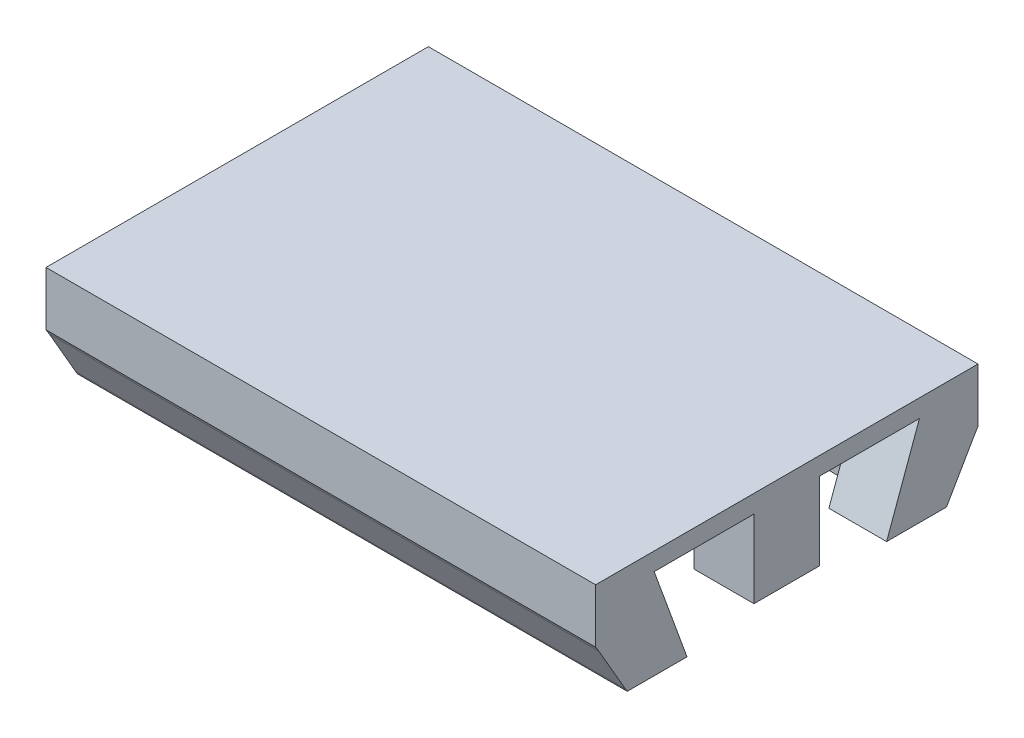
SolidWorks part; units mm, degrees
ref_plane "前视基准面" through (0, 0, 0) normal (0, 0, 1) x (1, 0, 0)
ref_plane "上视基准面" through (0, 0, 0) normal (0, 1, 0) x (1, 0, 0)
ref_plane "右视基准面" through (0, 0, 0) normal (1, 0, 0) x (0, 0, -1)
sketch "前视标记" plane through (0, 0, 0) normal (0, 0, 1) x (1, 0, 0)
  line L1 (0, 0) -> (58.42, 0)
  line L2 (0, 0) -> (0, 11.4935)
  line L3 (0, 11.4935) -> (58.42, 11.4935)
  line L4 (58.42, 0) -> (58.42, 11.4935)
sketch "上视标记" plane through (0, 0, 0) normal (0, 1, 0) x (1, 0, 0)
  line L1 (58.42, -40.64) -> (0, -40.64)
  line L3 (0, -40.64) -> (58.42, -40.64)
  line L4 (0, -40.64) -> (0, 0)
  line L5 (0, 0) -> (58.42, 0)
  line L6 (58.42, -40.64) -> (58.42, 0)
  line L7 (9.3133, -30.9271) -> (9.3133, -34.417)
  line L9 (9.3133, -6.223) -> (9.3133, -9.7129)
  line L10 (21.59, -34.417) -> (27.7283, -34.417)
  line L12 (58.42, -23.8125) -> (58.42, -16.8275)
  line L14 (58.42, -16.8275) -> (52.07, -16.8275)
  line L18 (52.07, -23.8125) -> (58.42, -23.8125)
  line L19 (52.07, -16.8275) -> (52.07, -23.8125)
  line L22 (52.2817, -30.9271) -> (52.2817, -34.417)
  line L23 (58.42, -30.9271) -> (52.2817, -30.9271)
  line L28 (46.1433, -30.9271) -> (40.005, -30.9271)
  line L30 (40.005, -30.9271) -> (40.005, -34.417)
  line L34 (46.1433, -34.417) -> (46.1433, -30.9271)
  line L35 (40.005, -34.417) -> (46.1433, -34.417)
  line L41 (33.8667, -34.417) -> (33.8667, -30.9271)
  line L42 (27.7283, -34.417) -> (33.8667, -34.417)
  line L47 (27.7283, -30.9271) -> (27.7283, -34.417)
  line L48 (33.8667, -30.9271) -> (27.7283, -30.9271)
  line L52 (21.59, -34.417) -> (21.59, -30.9271)
  line L53 (15.4517, -34.417) -> (21.59, -34.417)
  line L58 (21.59, -30.9271) -> (15.4517, -30.9271)
  line L60 (15.4517, -30.9271) -> (15.4517, -34.417)
  line L61 (3.175, -30.9271) -> (9.3133, -30.9271)
  line L63 (3.175, -9.7129) -> (3.175, -30.9271)
  line L65 (9.3133, -9.7129) -> (3.175, -9.7129)
  line L67 (9.3133, -34.417) -> (15.4517, -34.417)
  line L69 (40.005, -34.417) -> (33.8667, -34.417)
  line L71 (52.2817, -34.417) -> (46.1433, -34.417)
  line L73 (52.2817, -9.7129) -> (58.42, -9.7129)
  line L75 (52.2817, -6.223) -> (52.2817, -9.7129)
  line L77 (46.1433, -6.223) -> (52.2817, -6.223)
  line L82 (46.1433, -9.7129) -> (46.1433, -6.223)
  line L83 (40.005, -9.7129) -> (46.1433, -9.7129)
  line L88 (46.1433, -6.223) -> (40.005, -6.223)
  line L90 (40.005, -6.223) -> (40.005, -9.7129)
  line L91 (40.005, -6.223) -> (33.8667, -6.223)
  line L93 (21.59, -6.223) -> (27.7283, -6.223)
  line L98 (27.7283, -9.7129) -> (33.8667, -9.7129)
  line L100 (33.8667, -9.7129) -> (33.8667, -6.223)
  line L104 (27.7283, -6.223) -> (27.7283, -9.7129)
  line L105 (33.8667, -6.223) -> (27.7283, -6.223)
  line L107 (15.4517, -6.223) -> (9.3133, -6.223)
  line L113 (21.59, -9.7129) -> (21.59, -6.223)
  line L114 (15.4517, -9.7129) -> (21.59, -9.7129)
  line L119 (15.4517, -6.223) -> (15.4517, -9.7129)
  line L120 (21.59, -6.223) -> (15.4517, -6.223)
sketch "右视标记" plane through (0, 0, 0) normal (1, 0, 0) x (0, 0, -1)
  line L1 (-40.64, 11.4935) -> (0, 11.4935)
  line L2 (-40.64, 11.4935) -> (-40.64, 0)
  line L3 (-40.64, 0) -> (0, 0)
  line L4 (0, 11.4935) -> (0, 0)
  line L5 (-6.223, 9.5885) -> (-34.417, 9.5885)
  line L7 (-40.2997, 5.207) -> (-37.4767, 0.3175)
  line L10 (-34.417, 9.5885) -> (-30.9271, 0)
  line L12 (-23.8125, 9.5885) -> (-23.8125, 1.3335)
  line L13 (-23.8125, 1.3335) -> (-16.8275, 1.3335)
  line L14 (-3.1633, 0.3175) -> (-0.3403, 5.207)
  line L15 (-9.7129, 0) -> (-6.223, 9.5885)
  line L18 (-16.8275, 9.5885) -> (-23.8125, 9.5885)
  line L19 (-40.2997, 5.207) -> (-40.64, 5.7468)
  line L20 (-16.8275, 1.3335) -> (-16.8275, 9.5885)
  line L21 (-37.4767, 0.3175) -> (-37.2766, 0)
  line L22 (-0.3403, 5.207) -> (0, 5.7468)
  line L23 (-3.1633, 0.3175) -> (-3.3466, 0)
  circle A0 centre (-5.08, 4.7498) radius 1.1303
  point P16 (-20.32, 0)
  dimension "D1" = 5.08
  dimension "D2" = 4.7498
ref_plane "中切面" through (0, 0, 20.32) normal (0, 0, 1) x (1, 0, 0)
extrude "拉伸1" add sketch "右视标记" along normal up to vertex (58.42 mm away) contours L23 L14 L22 L4 L1 L2 L19 L7 L21 L3 A0 L20 L13 L12 L5 | L13 L20 L5 L12 | A0 region at (0, 11.0712, 20.32) region at (0, 4.8961, 32.3922) region at (0, 5.461, 20.32) up to point (58.42, 0, 0)
sketch "草图5" plane through (58.42, 0, 0) normal (1, 0, 0) x (0, 0, -1)
  line L0 (-0.3403, 5.207) -> (0, 5.7468) construction
  line L1 (-3.1633, 0.3175) -> (-0.3403, 5.207) construction
  line L2 (-3.1633, 0.3175) -> (-3.3466, 0) construction
  line L3 (-37.4767, 0.3175) -> (-37.2766, 0) construction
  line L4 (-40.2997, 5.207) -> (-37.4767, 0.3175) construction
  line L5 (-40.2997, 5.207) -> (-40.64, 5.7468) construction
  line L6 (-34.417, 9.5885) -> (-30.9271, 0) construction
  line L7 (-6.223, 9.5885) -> (-34.417, 9.5885) construction
  line L8 (-9.7129, 0) -> (-6.223, 9.5885) construction
  line L9 (-0.3403, 5.207) -> (0, 5.7468)
  line L10 (-3.1633, 0.3175) -> (-0.3403, 5.207)
  line L11 (-3.1633, 0.3175) -> (-3.3466, 0)
  line L12 (-37.4767, 0.3175) -> (-37.2766, 0)
  line L13 (-40.2997, 5.207) -> (-37.4767, 0.3175)
  line L14 (-40.2997, 5.207) -> (-40.64, 5.7468)
  line L15 (-34.417, 9.5885) -> (-30.9271, 0)
  line L16 (-6.223, 9.5885) -> (-34.417, 9.5885)
  line L17 (-9.7129, 0) -> (-6.223, 9.5885)
  line L18 (-30.9271, 0) -> (-9.7129, 0)
  line L22 (-23.8125, 9.5885) -> (-23.8125, 1.3335)
  line L23 (-23.8125, 1.3335) -> (-16.8275, 1.3335)
  line L24 (-16.8275, 1.3335) -> (-16.8275, 9.5885)
  line L25 (-16.8275, 9.5885) -> (-23.8125, 9.5885)
  line L26 (-23.8125, 9.5885) -> (-23.8125, 1.3335)
  line L27 (-23.8125, 1.3335) -> (-16.8275, 1.3335)
  line L28 (-16.8275, 1.3335) -> (-16.8275, 9.5885)
  line L29 (-16.8275, 9.5885) -> (-23.8125, 9.5885)
  line L30 (0, 11.4935) -> (-40.64, 11.4935)
  line L31 (0, 0) -> (0, 11.4935)
  line L32 (-40.64, 0) -> (0, 0)
  line L33 (-40.64, 11.4935) -> (-40.64, 0)
  line L34 (0, 11.4935) -> (-40.64, 11.4935)
  line L35 (0, 0) -> (0, 11.4935)
  line L36 (-40.64, 0) -> (0, 0)
  line L37 (-40.64, 11.4935) -> (-40.64, 0)
  circle A1 centre (-5.08, 4.7498) radius 1.1303
  circle A2 centre (-5.08, 4.7498) radius 1.1303
  dimension "D1" = 0
  dimension "D2" = 0
  dimension "D3" = 0
extrude "拉伸2" cut sketch "草图5" against normal up to vertex (55.245 mm away) contours L28 L27 L26 L16 L15 L18 L17 region at (58.42, 0.2978, 20.32) up to point (3.175, 0, 30.9271)
extrude "拉伸4" cut sketch "上视标记" along normal up to vertex (9.5885 mm away) contours L119 L107 L9 L65 L63 L61 L7 L67 L60 L58 L52 L10 L47 L48 L41 L69 L30 L28 L34 L71 L22 L23 L6 L18 L19 L14 L73 L75 L77 L82 L83 L90 L91 L100 L98 L104 L93 L113 L114 region at (29.9627, 0, 20.32) up to point (58.42, 9.5885, 23.8125)
sketch "草图6" plane through (0, 1.3335, 0) normal (0, -1, 0) x (1, 0, 0)
  line L4 (52.07, 23.8125) -> (52.07, 16.8275)
  line L5 (52.07, 16.8275) -> (58.42, 16.8275)
  line L6 (58.42, 16.8275) -> (58.42, 23.8125)
  line L7 (58.42, 23.8125) -> (52.07, 23.8125)
  line L8 (52.07, 23.8125) -> (52.07, 16.8275)
  line L9 (52.07, 16.8275) -> (58.42, 16.8275)
  line L10 (58.42, 16.8275) -> (58.42, 23.8125)
  line L11 (58.42, 23.8125) -> (52.07, 23.8125)
  dimension "D1" = 0
extrude "拉伸5" cut sketch "草图6" along normal through all
extrude "拉伸6" cut sketch "右视标记<4>" along normal blind 5 contours A0
sketch "右视标记<4>" plane through (0, 0, 0) normal (1, 0, 0) x (0, 0, -1) same geometry as "右视标记"
mirror "镜向1" about plane through (0, 0, 20.32) normal (0, 0, 1) of "拉伸6"
